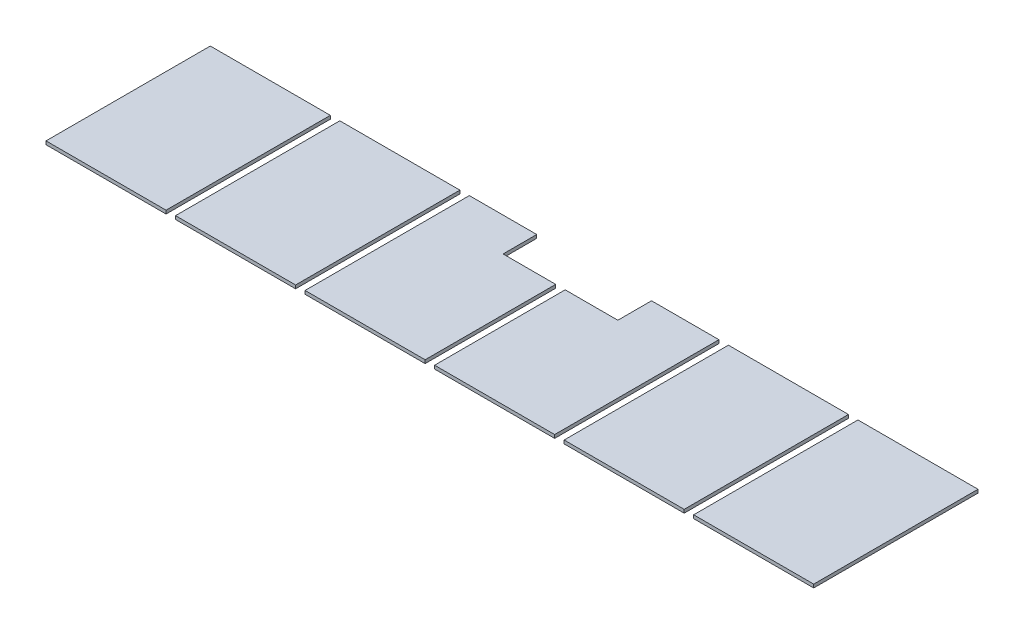
SolidWorks part; units mm, degrees
ref_plane "Front Plane" through (0, 0, 0) normal (0, 0, 1) x (1, 0, 0)
ref_plane "Top Plane" through (0, 0, 0) normal (0, 1, 0) x (1, 0, 0)
ref_plane "Right Plane" through (0, 0, 0) normal (1, 0, 0) x (0, 0, -1)
sketch "Sketch2" plane through (0, 0, 0) normal (0, 1, 0) x (1, 0, 0)
  line L4 (3073.4, 2044.7) -> (1625.6, 2044.7)
  line L5 (1625.6, 2044.7) -> (1625.6, 63.5)
  line L6 (1625.6, 63.5) -> (3073.4, 63.5)
  line L7 (3073.4, 63.5) -> (3073.4, 2044.7)
  line L8 (3073.4, 2044.7) -> (1625.6, 2044.7)
  line L9 (1625.6, 2044.7) -> (1625.6, 63.5)
  line L10 (1625.6, 63.5) -> (3073.4, 63.5)
  line L11 (3073.4, 63.5) -> (3073.4, 2044.7)
  line L12 (1511.3, 2044.7) -> (63.5, 2044.7)
  line L13 (63.5, 2044.7) -> (63.5, 63.5)
  line L14 (63.5, 63.5) -> (1511.3, 63.5)
  line L15 (1511.3, 63.5) -> (1511.3, 2044.7)
  line L16 (1511.3, 2044.7) -> (63.5, 2044.7)
  line L17 (63.5, 2044.7) -> (63.5, 63.5)
  line L18 (63.5, 63.5) -> (1511.3, 63.5)
  line L19 (1511.3, 63.5) -> (1511.3, 2044.7)
  line L20 (9321.8, 2044.7) -> (7874, 2044.7)
  line L21 (7874, 2044.7) -> (7874, 63.5)
  line L22 (7874, 63.5) -> (9321.8, 63.5)
  line L23 (9321.8, 63.5) -> (9321.8, 2044.7)
  line L24 (9321.8, 2044.7) -> (7874, 2044.7)
  line L25 (7874, 2044.7) -> (7874, 63.5)
  line L26 (7874, 63.5) -> (9321.8, 63.5)
  line L27 (9321.8, 63.5) -> (9321.8, 2044.7)
  line L28 (7759.7, 63.5) -> (7759.7, 2044.7)
  line L29 (6311.9, 63.5) -> (7759.7, 63.5)
  line L30 (6311.9, 2044.7) -> (6311.9, 63.5)
  line L31 (7759.7, 2044.7) -> (6311.9, 2044.7)
  line L32 (7759.7, 63.5) -> (7759.7, 2044.7)
  line L33 (6311.9, 63.5) -> (7759.7, 63.5)
  line L34 (6311.9, 2044.7) -> (6311.9, 63.5)
  line L35 (7759.7, 2044.7) -> (6311.9, 2044.7)
  line L36 (11976.1, 2298.7) -> (9436.1, 2298.7)
  line L37 (11976.1, 50.8) -> (11976.1, 2298.7)
  line L38 (6197.6, 2044.7) -> (5384.8, 2044.7)
  line L39 (6197.6, 63.5) -> (6197.6, 2044.7)
  line L40 (4749.8, 63.5) -> (6197.6, 63.5)
  line L41 (4749.8, 1638.3) -> (4749.8, 63.5)
  line L42 (5384.8, 1638.3) -> (4749.8, 1638.3)
  line L43 (5384.8, 2044.7) -> (5384.8, 1638.3)
  line L44 (6197.6, 2044.7) -> (5384.8, 2044.7)
  line L45 (6197.6, 63.5) -> (6197.6, 2044.7)
  line L46 (4749.8, 63.5) -> (6197.6, 63.5)
  line L47 (4749.8, 1638.3) -> (4749.8, 63.5)
  line L48 (5384.8, 1638.3) -> (4749.8, 1638.3)
  line L49 (5384.8, 2044.7) -> (5384.8, 1638.3)
  line L50 (3187.7, 2044.7) -> (3187.7, 63.5)
  line L51 (4000.5, 2044.7) -> (3187.7, 2044.7)
  line L52 (4000.5, 1638.3) -> (4000.5, 2044.7)
  line L53 (4635.5, 1638.3) -> (4000.5, 1638.3)
  line L54 (4635.5, 63.5) -> (4635.5, 1638.3)
  line L55 (3187.7, 63.5) -> (4635.5, 63.5)
  line L56 (3187.7, 2044.7) -> (3187.7, 63.5)
  line L57 (4000.5, 2044.7) -> (3187.7, 2044.7)
  line L58 (4000.5, 1638.3) -> (4000.5, 2044.7)
  line L59 (4635.5, 1638.3) -> (4000.5, 1638.3)
  line L60 (4635.5, 63.5) -> (4635.5, 1638.3)
  line L61 (3187.7, 63.5) -> (4635.5, 63.5)
  line L62 (9436.1, 50.8) -> (11976.1, 50.8)
  line L63 (9436.1, 2298.7) -> (9436.1, 50.8)
  line L64 (11976.1, 2298.7) -> (9436.1, 2298.7)
  line L65 (11976.1, 50.8) -> (11976.1, 2298.7)
  line L66 (9436.1, 50.8) -> (11976.1, 50.8)
  line L67 (9436.1, 2298.7) -> (9436.1, 50.8)
  dimension "D1" = 0
  dimension "D2" = 0
  dimension "D3" = 0
  dimension "D4" = 0
  dimension "D5" = 0
  dimension "D6" = 0
  dimension "D7" = 0
extrude "Boss-Extrude1" add sketch "Sketch2" along normal up to surface (40.64 mm away) contours L18 L19 L16 L17 | L10 L11 L8 L9 | L56 L61 L60 L59 L58 L57 | L44 L49 L48 L47 L46 L45 | L32 L35 L34 L33 | L26 L27 L24 L25 region at (2349.5, 0, -1054.1) region at (787.4, 0, -1054.1) region at (8597.9, 0, -1054.1) region at (7035.8, 0, -1054.1) region at (5513.878, 0, -976.2552) region at (3871.422, 0, -976.2552)
